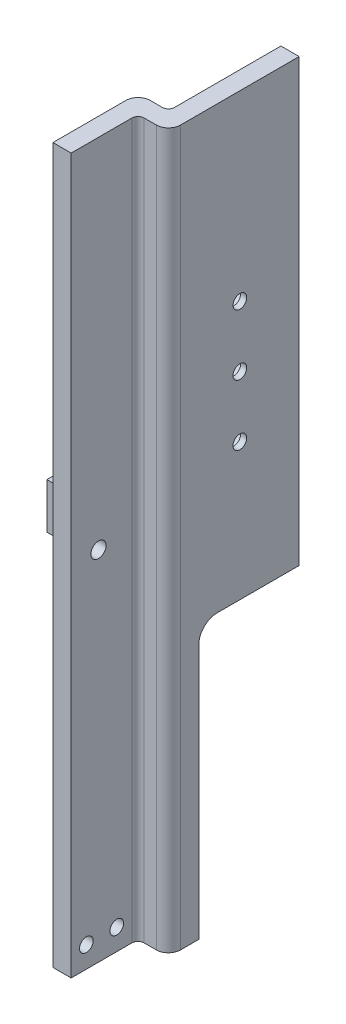
SolidWorks part; units mm, degrees
ref_plane "Piano frontale" through (0, 0, 0) normal (0, 0, 1) x (1, 0, 0)
ref_plane "Piano superiore" through (0, 0, 0) normal (0, 1, 0) x (1, 0, 0)
ref_plane "Piano destro" through (0, 0, 0) normal (1, 0, 0) x (0, 0, -1)
ref_plane "Piano1" through (6, 0, 0) normal (1, 0, 0) x (0, 0, -1)
sketch "Schizzo1" plane through (6, 0, 0) normal (1, 0, 0) x (0, 0, -1)
  line L0 (-28, 0) -> (37, 0)
  line L1 (37, 0) -> (37, 235)
  line L2 (37, 235) -> (-28, 235)
  line L3 (-28, 235) -> (-28, 0)
  dimension "D1" = 65
  dimension "D2" = 235
extrude "Estrusione-Estrusione1" add sketch "Schizzo1" against normal blind 16
sketch "Schizzo2" plane through (0, 0, 0) normal (0, -1, 0) x (1, 0, 0)
  line L0 (-10, -37) -> (0, -37)
  line L1 (0, -37) -> (0, 0)
  line L2 (0, 0) -> (-10, 0)
  line L3 (-10, 0) -> (-10, -37)
  line L4 (6, 28) -> (6, -37) construction
  dimension "D1" = 6
  dimension "D2" = 16
  dimension "D3" = 28
  dimension "D4" = 65
extrude "Taglio-Estrusione1" cut sketch "Schizzo2" against normal through all
sketch "Schizzo3" plane through (6, 0, 0) normal (1, 0, 0) x (0, 0, -1)
  line L0 (37, 0) -> (37, 90)
  line L1 (37, 90) -> (4, 90)
  line L2 (4, 90) -> (4, 0)
  line L3 (4, 0) -> (37, 0)
  line L4 (-28, 0) -> (37, 0) construction
  line L5 (-28, 235) -> (-28, 0) construction
  dimension "D1" = 32
  dimension "D2" = 65
  dimension "D3" = 90
extrude "Taglio-Estrusione2" cut sketch "Schizzo3" against normal through all
sketch "Schizzo4" plane through (0, 0, 0) normal (0, -1, 0) x (1, 0, 0)
  line L0 (6, 28) -> (-4, 28)
  line L1 (-4, 28) -> (-4, 6)
  line L2 (-4, 6) -> (6, 6)
  line L3 (6, 6) -> (6, 28)
  line L4 (6, 28) -> (6, -4) construction
  dimension "D1" = 10
  dimension "D2" = 22
extrude "Taglio-Estrusione3" cut sketch "Schizzo4" against normal through all
hole_wizard "Foro lamato per Vite M4 a testa esagonale-1" positions "Schizzo6" profile "Schizzo5" counterbore size "M4" standard "Ansi Metric"
sketch "Schizzo6" plane through (0, 0, 0) normal (-1, 0, 0) x (0, 0, 1)
  point P0 (-17.5, 175)
  point P1 (-17.5, 155)
  point P2 (-17.5, 135)
sketch "Schizzo5" plane through (0, 175, -17.5) normal (0, 1, 0) x (0, 0, 1)
  line L0 (0, 0) -> (0, 6)
  line L1 (0, 6) -> (2.25, 6)
  line L3 (2.25, 6) -> (2.25, 4)
  line L4 (2.25, 4) -> (4, 4)
  line L5 (4, 4) -> (4, 0)
  line L7 (4, 0) -> (0, 0)
  line L11 (0, -6.35) -> (0, 107.95) construction
  dimension "Thru Hole Dia." = 4.5
  dimension "Thru Hole Depth" = 6
  dimension "C'Bore Dia." = 8
  dimension "C'Bore Depth" = 4
fillet "Raccordo1" radius 2 2 edges at (0, 117.5, 0) (-4, 117.5, 6) tangent propagation no
fillet "Raccordo2" radius 4 2 edges at (-10, 117.5, 0) (6, 117.5, 6) tangent propagation no
fillet "Raccordo3" radius 6 1 edges at (3, 90, -4) tangent propagation no
hole_wizard "Foro per Vite M4-1" positions "Schizzo8" profile "Schizzo9" hole size "M4" standard "ISO"
sketch "Schizzo8" plane through (-4, 0, 0) normal (1, 0, 0) x (0, 0, -1)
  line L0 (-28, 0) -> (-8, 0) construction
  line L1 (-28, 235) -> (-28, 0) construction
  point P0 (-23, 7)
  point P7 (-13, 7)
  dimension "D1" = 7
  dimension "D2" = 5
  dimension "D3" = 10
  dimension "D4" = 7
sketch "Schizzo9" plane through (-4, 7, 23) normal (0, 1, 0) x (0, 0, -1)
  line L0 (0, 0) -> (0, 189.3519)
  line L1 (0, 189.3519) -> (2.25, 188)
  line L2 (2.25, 188) -> (2.25, 0)
  line L5 (2.25, 0) -> (0, 0)
  line L10 (0, 189.3519) -> (-2.25, 188) construction
  line L11 (0, -6.35) -> (0, 107.95) construction
  dimension "Hole Dia." = 4.5
  dimension "Hole Depth" = 188
  dimension "Drill Angle" = 118
sketch "Schizzo10" plane through (-10, 0, 0) normal (-1, 0, 0) x (0, 0, 1)
  line L0 (28, 0) -> (4, 0) construction
  line L1 (12, 110) -> (15, 110)
  line L2 (12, 110) -> (12, 125)
  line L3 (12, 125) -> (15, 125)
  line L4 (15, 110) -> (15, 125)
  line L5 (4, 235) -> (4, 0) construction
  dimension "D1" = 3
  dimension "D2" = 15
  dimension "D3" = 110
  dimension "D4" = 8
extrude "Estrusione-Estrusione2" add sketch "Schizzo10" along normal blind 15
sketch "Schizzo11" plane through (-10, 0, 0) normal (-1, 0, 0) x (0, 0, 1)
  line L0 (15, 117.5) -> (19, 117.5) construction
  line L1 (15, 110) -> (15, 125) construction
  circle A0 centre (19, 117.5) radius 2.5
  dimension "D1" = 5
  dimension "D2" = 4
extrude "Taglio-Estrusione4" cut sketch "Schizzo11" against normal blind 10
chamfer "Smusso1" distance 8 angle 45 1 edges at (-10, 117.5, 12)
